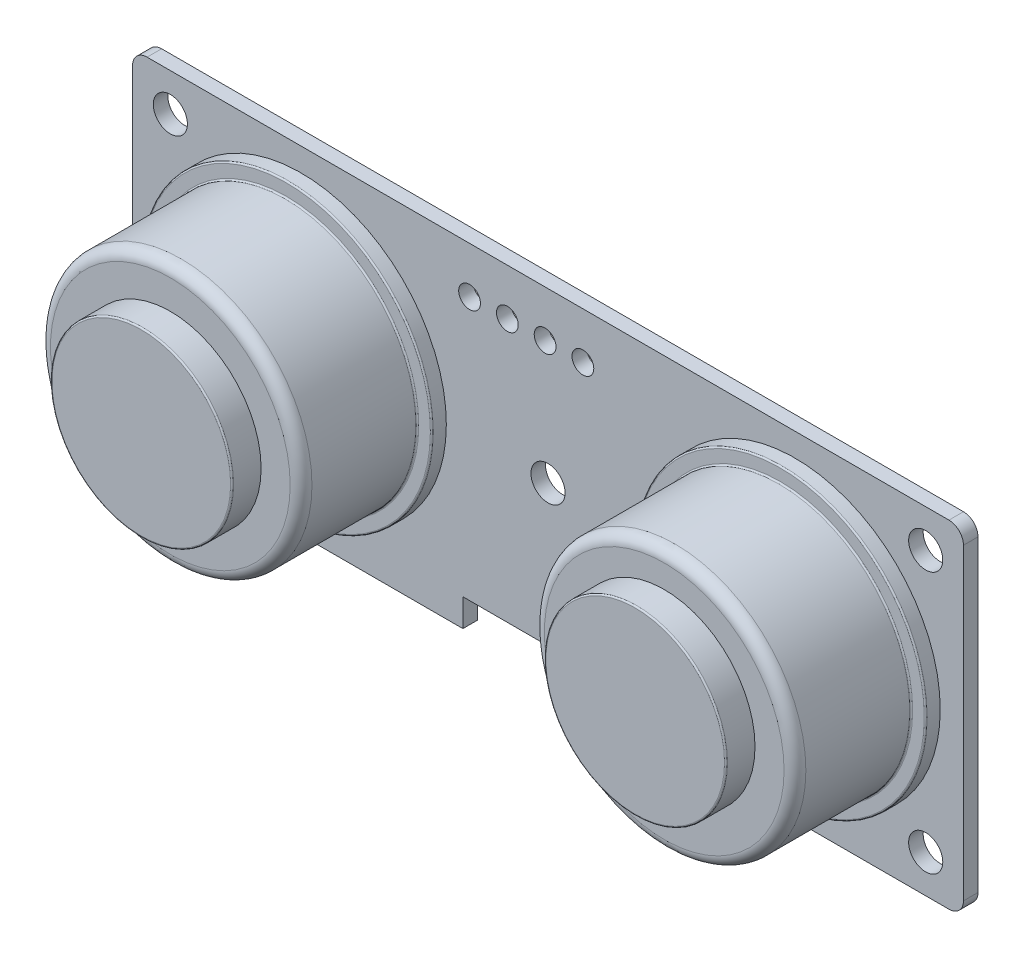
SolidWorks part; units mm, degrees
ref_plane "Ön Düzlem" through (0, 0, 0) normal (0, 0, 1) x (1, 0, 0)
ref_plane "Üst Düzlem" through (0, 0, 0) normal (0, 1, 0) x (1, 0, 0)
ref_plane "Sağ Düzlem" through (0, 0, 0) normal (1, 0, 0) x (0, 0, -1)
sketch "Çizim1" plane through (0, 0, 0) normal (0, 0, 1) x (1, 0, 0)
  line L0 (-5.8595, -11.6) -> (-27.6, -11.6)
  line L1 (27.6, 11.6) -> (-27.6, 11.6)
  line L2 (28.6, 10.6) -> (28.6, -10.6)
  line L3 (27.6, -11.6) -> (5.8595, -11.6)
  line L4 (-28.6, 10.6) -> (-28.6, -10.6)
  line L5 (0, 0) -> (0, -9.6979) construction
  line L6 (0, 0) -> (-28.6, 0) construction
  line L7 (-5.8595, -9.6979) -> (5.8595, -9.6979)
  line L8 (-5.8595, -9.6979) -> (-5.8595, -11.6)
  line L10 (5.8595, -9.6979) -> (5.8595, -11.6)
  line L11 (0, 0) -> (0, 11.6) construction
  line L12 (-26, 9) -> (26, 9) construction
  line L13 (-17.1, 5.1) -> (-17.1, -5.1) construction
  line L14 (-5.4, 8.4) -> (2.6, 8.4) construction
  arc A0 (28.6, -10.6) -> (27.6, -11.6) centre (27.6, -10.6) cw
  arc A1 (27.6, 11.6) -> (28.6, 10.6) centre (27.6, 10.6) cw
  arc A2 (-27.6, -11.6) -> (-28.6, -10.6) centre (-27.6, -10.6) cw
  arc A3 (-27.6, 11.6) -> (-28.6, 10.6) centre (-27.6, 10.6) ccw
  circle A4 centre (-26, 9) radius 1.175
  circle A5 centre (26, 9) radius 1.175
  circle A6 centre (26, -9) radius 1.175
  circle A7 centre (-26, -9) radius 1.175
  circle A8 centre (0, 0) radius 1.175
  circle A9 centre (-17.1, 5.1) radius 0.9
  circle A10 centre (-17.1, -5.1) radius 0.9
  circle A11 centre (17.1, -5.1) radius 0.9
  circle A12 centre (17.1, 5.1) radius 0.9
  circle A13 centre (-5.4, 8.4) radius 0.75
  circle A14 centre (-2.8, 8.4) radius 0.75
  circle A15 centre (-0.2, 8.4) radius 0.75
  circle A16 centre (2.4, 8.4) radius 0.75
  point P1 (0, 5.8)
  point P29 (0, 9)
  dimension "D3" = 1
  dimension "D4" = 2.35
  dimension "D5" = 52
  dimension "D6" = 2.35
  dimension "D7" = 6.5
  dimension "D8" = 6.5
  dimension "D9" = 2.6
  dimension "D10" = 2.6
  dimension "D11" = 2.6
  dimension "D12" = 2.6
  dimension "D13" = 18
  dimension "D15" = 1.8
  dimension "D16" = 1.8
  dimension "D20" = 1.5
  dimension "D1" = 57.2
  dimension "D2" = 23.2
  dimension "D14" = 11.5
  dimension "D17" = 8
  dimension "D18" = 3.2
  dimension "D19" = 23.2
  dimension "D21" = 4
extrude "Yükseklik-Ekstrüzyon1" add sketch "Çizim1" along normal blind 1
sketch "Çizim2" plane through (0, 0, 1) normal (0, 0, 1) x (1, 0, 0)
  line L3 (-17, 0) -> (17, 0) construction
  line L4 (0, 1.175) -> (0, -1.175) construction
  circle A0 centre (-17, 0) radius 10
  circle A1 centre (17, 0) radius 10
  circle A2 centre (0, 0) radius 1.175 construction
  point P8 (0, 0)
  dimension "D1" = 20
  dimension "D2" = 34
  dimension "D6" = 20
extrude "Yükseklik-Ekstrüzyon2" add sketch "Çizim2" along normal blind 1 separate body
sketch "Çizim3" plane through (0, 0, 2) normal (0, 0, 1) x (1, 0, 0)
  circle A0 centre (-17, 0) radius 9
  circle A1 centre (17, 0) radius 9
  dimension "D1" = 18
extrude "Yükseklik-Ekstrüzyon3" add sketch "Çizim3" along normal blind 8
sketch "Çizim4" plane through (0, 0, 10) normal (0, 0, 1) x (1, 0, 0)
  circle A0 centre (-17, 0) radius 6.25
  circle A1 centre (17, 0.4139) radius 6.25
  dimension "D1" = 12.5
extrude "Yükseklik-Ekstrüzyon4" add sketch "Çizim4" along normal blind 2 separate body
fillet "Radyus1" radius 0.75 1 edges at (-8, 0, 10)
fillet "Radyus2" radius 0.75 1 edges at (26, 0, 10)
fillet "Radyus3" radius 0.1 1 edges at (-10.75, 0, 12)
fillet "Radyus4" radius 0.1 1 edges at (23.25, 0.4139, 12)
fillet "Radyus5" radius 0.1 2 edges at (-7, 0, 2) (-8, 0, 2)
fillet "Radyus6" radius 0.1 2 edges at (27, 0, 2) (26, 0, 2)
sketch "Çizim10" plane through (0, 0, 0) normal (0, 0, -1) x (-1, 0, 0)
  line L0 (-13.9117, 4.4086) -> (-5.092, 4.4086)
  line L2 (-13.9117, 4.4086) -> (-13.9117, 1.1362)
  line L3 (-13.9117, 1.1362) -> (-5.092, 1.1362)
  line L4 (-5.092, 4.4086) -> (-5.092, 1.1362)
  line L5 (4.9259, -2.3247) -> (9.1781, -2.3247)
  line L6 (4.9259, -2.3247) -> (4.9259, -8.8397)
  line L7 (4.9259, -8.8397) -> (9.1781, -8.8397)
  line L8 (9.1781, -2.3247) -> (9.1781, -8.8397)
  line L21 (-22.8585, 6.7991) -> (-19.9987, 6.7991)
  line L22 (-22.8585, 6.7991) -> (-22.8585, 5.55)
  line L23 (-22.8585, 5.55) -> (-19.9987, 5.55)
  line L24 (-19.9987, 6.7991) -> (-19.9987, 5.55)
  line L54 (-13.9117, 2.7724) -> (-5.092, 2.7724) construction
  line L83 (-21.4286, 5.55) -> (-21.4286, 6.7991) construction
  line L137 (7.052, -2.3247) -> (7.052, -8.8397) construction
  line L180 (11.2809, 9.5742) -> (12.8042, 9.5742)
  line L181 (11.2809, 7.4761) -> (12.8042, 7.4761)
  line L184 (11.2809, 9.5742) -> (11.2809, 7.4761)
  line L185 (12.8042, 9.5742) -> (12.8042, 7.4761)
  line L187 (21.6705, 8.5491) -> (21.6705, 6.4509)
  line L189 (23.1938, 8.5491) -> (23.1938, 6.4509)
  line L192 (21.6705, 8.5491) -> (23.1938, 8.5491)
  line L196 (21.6705, 6.4509) -> (23.1938, 6.4509)
  line L210 (15.5044, 1.6587) -> (15.5044, 2.9078)
  line L212 (12.6446, 1.6587) -> (12.6446, 2.9078)
  line L214 (15.5044, 1.6587) -> (12.6446, 1.6587)
  line L220 (15.5044, 2.9078) -> (12.6446, 2.9078)
  line L222 (14.0745, 2.9078) -> (14.0745, 1.6587) construction
  line L227 (-3.9914, -8.0653) -> (-1.1316, -8.0653)
  line L229 (-3.9914, -6.8162) -> (-1.1316, -6.8162)
  line L236 (-1.1316, -6.8162) -> (-1.1316, -8.0653)
  line L237 (-3.9914, -6.8162) -> (-3.9914, -8.0653)
  line L243 (-2.5615, -8.0653) -> (-2.5615, -6.8162) construction
  line L244 (8.651, 5.9274) -> (8.651, 3.8292)
  line L245 (10.1743, 5.9274) -> (10.1743, 3.8292)
  line L246 (8.651, 3.8292) -> (10.1743, 3.8292)
  line L247 (8.651, 5.9274) -> (10.1743, 5.9274)
  point P92 (-21.4286, 6.8907)
  point P209 (14.0745, 1.5672)
  point P224 (-2.5615, -6.7247)
extrude "Yükseklik-Ekstrüzyon7" add sketch "Çizim10" along normal blind 1
sketch "Çizim11" plane through (0, 0, 0) normal (0, 0, -1) x (-1, 0, 0)
  line L0 (11.2809, 10.1474) -> (12.8042, 10.1474)
  line L1 (11.2809, 10.1474) -> (11.2809, 9.6474)
  line L2 (11.2809, 6.8956) -> (12.8042, 6.8956)
  line L3 (12.8042, 10.1474) -> (12.8042, 9.6474)
  line L4 (-13.7663, 4.4644) -> (-13.7663, 5.8674)
  line L5 (-13.7663, 5.8674) -> (-13.2262, 5.8674)
  line L6 (-13.2262, 4.4644) -> (-13.2262, 5.8674)
  line L7 (-13.7663, 4.4644) -> (-13.2262, 4.4644)
  line L8 (-11.8762, 4.4644) -> (-11.8762, 5.8674)
  line L9 (-12.4163, 5.8674) -> (-11.8762, 5.8674)
  line L10 (-12.4163, 4.4644) -> (-12.4163, 5.8674)
  line L11 (-12.4163, 4.4644) -> (-11.8762, 4.4644)
  line L12 (-10.5262, 4.4644) -> (-10.5262, 5.8674)
  line L13 (-11.0663, 5.8674) -> (-10.5262, 5.8674)
  line L14 (-11.0663, 4.4644) -> (-11.0663, 5.8674)
  line L15 (-11.0663, 4.4644) -> (-10.5262, 4.4644)
  line L16 (-9.1762, 4.4644) -> (-9.1762, 5.8674)
  line L17 (-9.7163, 5.8674) -> (-9.1762, 5.8674)
  line L18 (-9.7163, 4.4644) -> (-9.7163, 5.8674)
  line L19 (-9.7163, 4.4644) -> (-9.1762, 4.4644)
  line L20 (-7.8262, 4.4644) -> (-7.8262, 5.8674)
  line L21 (-8.3663, 5.8674) -> (-7.8262, 5.8674)
  line L22 (-8.3663, 4.4644) -> (-8.3663, 5.8674)
  line L23 (-8.3663, 4.4644) -> (-7.8262, 4.4644)
  line L24 (-6.4762, 4.4644) -> (-6.4762, 5.8674)
  line L25 (-7.0163, 5.8674) -> (-6.4762, 5.8674)
  line L26 (-7.0163, 4.4644) -> (-7.0163, 5.8674)
  line L27 (-7.0163, 4.4644) -> (-6.4762, 4.4644)
  line L28 (-5.1262, 4.4644) -> (-5.1262, 5.8674)
  line L29 (-5.6663, 5.8674) -> (-5.1262, 5.8674)
  line L30 (-5.6663, 4.4644) -> (-5.6663, 5.8674)
  line L31 (-5.6663, 4.4644) -> (-5.1262, 4.4644)
  line L32 (-5.6663, 1.0904) -> (-5.1262, 1.0904)
  line L33 (-5.6663, 1.0904) -> (-5.6663, -0.3126)
  line L34 (-5.6663, -0.3126) -> (-5.1262, -0.3126)
  line L35 (-5.1262, 1.0904) -> (-5.1262, -0.3126)
  line L36 (-7.0163, 1.0904) -> (-6.4762, 1.0904)
  line L37 (-7.0163, 1.0904) -> (-7.0163, -0.3126)
  line L38 (-7.0163, -0.3126) -> (-6.4762, -0.3126)
  line L39 (-6.4762, 1.0904) -> (-6.4762, -0.3126)
  line L40 (-8.3663, 1.0904) -> (-7.8262, 1.0904)
  line L41 (-8.3663, 1.0904) -> (-8.3663, -0.3126)
  line L42 (-8.3663, -0.3126) -> (-7.8262, -0.3126)
  line L43 (-7.8262, 1.0904) -> (-7.8262, -0.3126)
  line L44 (-9.7163, 1.0904) -> (-9.1762, 1.0904)
  line L45 (-9.7163, 1.0904) -> (-9.7163, -0.3126)
  line L46 (-9.7163, -0.3126) -> (-9.1762, -0.3126)
  line L47 (-9.1762, 1.0904) -> (-9.1762, -0.3126)
  line L48 (-11.0663, 1.0904) -> (-10.5262, 1.0904)
  line L49 (-11.0663, 1.0904) -> (-11.0663, -0.3126)
  line L50 (-11.0663, -0.3126) -> (-10.5262, -0.3126)
  line L51 (-10.5262, 1.0904) -> (-10.5262, -0.3126)
  line L52 (-12.4163, 1.0904) -> (-11.8762, 1.0904)
  line L53 (-12.4163, 1.0904) -> (-12.4163, -0.3126)
  line L54 (-12.4163, -0.3126) -> (-11.8762, -0.3126)
  line L55 (-11.8762, 1.0904) -> (-11.8762, -0.3126)
  line L56 (-13.7663, 1.0904) -> (-13.2262, 1.0904)
  line L57 (-13.2262, 1.0904) -> (-13.2262, -0.3126)
  line L58 (-13.7663, -0.3126) -> (-13.2262, -0.3126)
  line L59 (-13.7663, 1.0904) -> (-13.7663, -0.3126)
  line L60 (-22.8585, 5.505) -> (-22.0979, 5.505)
  line L61 (-22.8585, 5.505) -> (-22.8585, 4.6135)
  line L62 (-22.8585, 4.6135) -> (-22.0979, 4.6135)
  line L63 (-22.0979, 5.505) -> (-22.0979, 4.6135)
  line L64 (-19.9987, 4.6135) -> (-20.7593, 4.6135)
  line L65 (-20.7593, 5.505) -> (-20.7593, 4.6135)
  line L66 (-19.9987, 5.505) -> (-20.7593, 5.505)
  line L67 (-19.9987, 5.505) -> (-19.9987, 4.6135)
  line L68 (-21.9148, 6.8541) -> (-20.9424, 6.8541)
  line L69 (-20.9424, 6.8541) -> (-20.9424, 7.6725)
  line L70 (-20.9424, 7.6725) -> (-21.9148, 7.6725)
  line L71 (-21.9148, 6.8541) -> (-21.9148, 7.6725)
  line L72 (3.2713, -2.9897) -> (3.2713, -3.4612)
  line L73 (3.2713, -2.3197) -> (4.8588, -2.3197)
  line L74 (3.2713, -2.3197) -> (3.2713, -2.7912)
  line L75 (3.2713, -2.7912) -> (4.8588, -2.7912)
  line L76 (4.8588, -2.3197) -> (4.8588, -2.7912)
  line L77 (3.2713, -2.9897) -> (4.8588, -2.9897)
  line L78 (4.8588, -2.9897) -> (4.8588, -3.4612)
  line L79 (3.2713, -3.4612) -> (4.8588, -3.4612)
  line L80 (3.2713, -3.6597) -> (3.2713, -4.1312)
  line L81 (3.2713, -3.6597) -> (4.8588, -3.6597)
  line L82 (4.8588, -3.6597) -> (4.8588, -4.1312)
  line L83 (3.2713, -4.1312) -> (4.8588, -4.1312)
  line L84 (3.2713, -4.3297) -> (3.2713, -4.8012)
  line L85 (3.2713, -4.3297) -> (4.8588, -4.3297)
  line L86 (4.8588, -4.3297) -> (4.8588, -4.8012)
  line L87 (3.2713, -4.8012) -> (4.8588, -4.8012)
  line L88 (3.2713, -4.9997) -> (3.2713, -5.4712)
  line L89 (3.2713, -4.9997) -> (4.8588, -4.9997)
  line L90 (4.8588, -4.9997) -> (4.8588, -5.4712)
  line L91 (3.2713, -5.4712) -> (4.8588, -5.4712)
  line L92 (3.2713, -5.6697) -> (3.2713, -6.1412)
  line L93 (3.2713, -5.6697) -> (4.8588, -5.6697)
  line L94 (4.8588, -5.6697) -> (4.8588, -6.1412)
  line L95 (3.2713, -6.1412) -> (4.8588, -6.1412)
  line L96 (3.2713, -6.3397) -> (3.2713, -6.8112)
  line L97 (3.2713, -6.3397) -> (4.8588, -6.3397)
  line L98 (4.8588, -6.3397) -> (4.8588, -6.8112)
  line L99 (3.2713, -6.8112) -> (4.8588, -6.8112)
  line L100 (3.2713, -7.0097) -> (3.2713, -7.4812)
  line L101 (3.2713, -7.0097) -> (4.8588, -7.0097)
  line L102 (4.8588, -7.0097) -> (4.8588, -7.4812)
  line L103 (3.2713, -7.4812) -> (4.8588, -7.4812)
  line L104 (3.2713, -7.6797) -> (3.2713, -8.1512)
  line L105 (3.2713, -7.6797) -> (4.8588, -7.6797)
  line L106 (4.8588, -7.6797) -> (4.8588, -8.1512)
  line L107 (3.2713, -8.1512) -> (4.8588, -8.1512)
  line L108 (3.2713, -8.3497) -> (3.2713, -8.8212)
  line L109 (3.2713, -8.3497) -> (4.8588, -8.3497)
  line L110 (4.8588, -8.3497) -> (4.8588, -8.8212)
  line L111 (3.2713, -8.8212) -> (4.8588, -8.8212)
  line L112 (10.8327, -8.8212) -> (9.2452, -8.8212)
  line L113 (9.2452, -8.3497) -> (9.2452, -8.8212)
  line L114 (10.8327, -8.3497) -> (9.2452, -8.3497)
  line L115 (10.8327, -8.3497) -> (10.8327, -8.8212)
  line L116 (10.8327, -8.1512) -> (9.2452, -8.1512)
  line L117 (9.2452, -7.6797) -> (9.2452, -8.1512)
  line L118 (10.8327, -7.6797) -> (9.2452, -7.6797)
  line L119 (10.8327, -7.6797) -> (10.8327, -8.1512)
  line L120 (10.8327, -7.4812) -> (9.2452, -7.4812)
  line L121 (9.2452, -7.0097) -> (9.2452, -7.4812)
  line L122 (10.8327, -7.0097) -> (9.2452, -7.0097)
  line L123 (10.8327, -7.0097) -> (10.8327, -7.4812)
  line L124 (10.8327, -6.8112) -> (9.2452, -6.8112)
  line L125 (9.2452, -6.3397) -> (9.2452, -6.8112)
  line L126 (10.8327, -6.3397) -> (9.2452, -6.3397)
  line L127 (10.8327, -6.3397) -> (10.8327, -6.8112)
  line L128 (10.8327, -6.1412) -> (9.2452, -6.1412)
  line L129 (9.2452, -5.6697) -> (9.2452, -6.1412)
  line L130 (10.8327, -5.6697) -> (9.2452, -5.6697)
  line L131 (10.8327, -5.6697) -> (10.8327, -6.1412)
  line L132 (10.8327, -5.4712) -> (9.2452, -5.4712)
  line L133 (9.2452, -4.9997) -> (9.2452, -5.4712)
  line L134 (10.8327, -4.9997) -> (9.2452, -4.9997)
  line L135 (10.8327, -4.9997) -> (10.8327, -5.4712)
  line L136 (10.8327, -4.8012) -> (9.2452, -4.8012)
  line L137 (9.2452, -4.3297) -> (9.2452, -4.8012)
  line L138 (10.8327, -4.3297) -> (9.2452, -4.3297)
  line L139 (10.8327, -4.3297) -> (10.8327, -4.8012)
  line L140 (10.8327, -4.1312) -> (9.2452, -4.1312)
  line L141 (9.2452, -3.6597) -> (9.2452, -4.1312)
  line L142 (10.8327, -3.6597) -> (9.2452, -3.6597)
  line L143 (10.8327, -3.6597) -> (10.8327, -4.1312)
  line L144 (10.8327, -3.4612) -> (9.2452, -3.4612)
  line L145 (9.2452, -2.9897) -> (9.2452, -3.4612)
  line L146 (10.8327, -2.9897) -> (9.2452, -2.9897)
  line L147 (9.2452, -2.3197) -> (9.2452, -2.7912)
  line L148 (10.8327, -2.7912) -> (9.2452, -2.7912)
  line L149 (10.8327, -2.3197) -> (10.8327, -2.7912)
  line L150 (10.8327, -2.3197) -> (9.2452, -2.3197)
  line L151 (10.8327, -2.9897) -> (10.8327, -3.4612)
  line L152 (11.2809, 9.6474) -> (12.8042, 9.6474)
  line L153 (11.2809, 7.3956) -> (12.8042, 7.3956)
  line L154 (11.2809, 7.3956) -> (11.2809, 6.8956)
  line L155 (12.8042, 7.3956) -> (12.8042, 6.8956)
  line L156 (23.1938, 9.1223) -> (23.1938, 8.6223)
  line L157 (23.1938, 6.3705) -> (23.1938, 5.8705)
  line L158 (21.6705, 9.1223) -> (21.6705, 8.6223)
  line L159 (21.6705, 8.6223) -> (23.1938, 8.6223)
  line L160 (21.6705, 5.8705) -> (23.1938, 5.8705)
  line L161 (21.6705, 6.3705) -> (21.6705, 5.8705)
  line L162 (21.6705, 6.3705) -> (23.1938, 6.3705)
  line L163 (21.6705, 9.1223) -> (23.1938, 9.1223)
  line L164 (14.7438, 2.9628) -> (14.7438, 3.8543)
  line L165 (12.6446, 2.9628) -> (13.4052, 2.9628)
  line L166 (13.5883, 1.6137) -> (13.5883, 0.7953)
  line L167 (15.5044, 2.9628) -> (15.5044, 3.8543)
  line L168 (15.5044, 2.9628) -> (14.7438, 2.9628)
  line L169 (12.6446, 3.8543) -> (13.4052, 3.8543)
  line L170 (14.5607, 1.6137) -> (14.5607, 0.7953)
  line L171 (13.4052, 2.9628) -> (13.4052, 3.8543)
  line L172 (14.5607, 1.6137) -> (13.5883, 1.6137)
  line L173 (15.5044, 3.8543) -> (14.7438, 3.8543)
  line L174 (12.6446, 2.9628) -> (12.6446, 3.8543)
  line L175 (13.5883, 0.7953) -> (14.5607, 0.7953)
  line L176 (-2.0753, -6.7612) -> (-2.0753, -5.9428)
  line L177 (-1.8922, -8.1103) -> (-1.8922, -9.0018)
  line L178 (-3.2308, -8.1103) -> (-3.2308, -9.0018)
  line L179 (-1.1316, -9.0018) -> (-1.8922, -9.0018)
  line L180 (-3.0477, -6.7612) -> (-2.0753, -6.7612)
  line L181 (-3.9914, -8.1103) -> (-3.9914, -9.0018)
  line L182 (-3.9914, -8.1103) -> (-3.2308, -8.1103)
  line L183 (-3.9914, -9.0018) -> (-3.2308, -9.0018)
  line L184 (-3.0477, -6.7612) -> (-3.0477, -5.9428)
  line L185 (-1.1316, -8.1103) -> (-1.8922, -8.1103)
  line L186 (-1.1316, -8.1103) -> (-1.1316, -9.0018)
  line L187 (-2.0753, -5.9428) -> (-3.0477, -5.9428)
  line L188 (10.1743, 6.5142) -> (10.1743, 6.0142)
  line L189 (8.651, 6.5142) -> (8.651, 6.0142)
  line L190 (8.651, 3.7624) -> (8.651, 3.2624)
  line L191 (10.1743, 3.7624) -> (10.1743, 3.2624)
  line L192 (8.651, 6.0142) -> (10.1743, 6.0142)
  line L193 (8.651, 6.5142) -> (10.1743, 6.5142)
  line L194 (8.651, 3.7624) -> (10.1743, 3.7624)
  line L195 (8.651, 3.2624) -> (10.1743, 3.2624)
extrude "Yükseklik-Ekstrüzyon8" add sketch "Çizim11" along normal blind 1
fillet "Radyus8" radius 0.5 49 edges at (3.6111, -9.0018, -1) (1.5119, -9.0018, -1) (2.5615, -5.9428, -1) (-3.2713, -2.5555, -1) (-3.2713, -3.2255, -1) (-3.2713, -3.8955, -1) (-3.2713, -4.5655, -1) (-3.2713, -5.2355, -1) (-3.2713, -5.9055, -1) (-3.2713, -6.5755, -1) (-3.2713, -7.2455, -1) (-3.2713, -7.9155, -1) (-3.2713, -8.5855, -1) (-10.8327, -8.5855, -1) (-10.8327, -7.9155, -1) (-10.8327, -7.2455, -1) (-10.8327, -6.5755, -1) (-10.8327, -5.9055, -1) (-10.8327, -5.2355, -1) (-10.8327, -4.5655, -1) (-10.8327, -3.8955, -1) (-10.8327, -3.2255, -1) (-10.8327, -2.5555, -1) (-14.0745, 0.7953, -1) (-15.1241, 3.8543, -1) (-13.0249, 3.8543, -1) (-22.4322, 5.8705, -1) (-22.4322, 9.1223, -1) (-12.0425, 6.8956, -1) (-12.0425, 10.1474, -1) (5.3962, -0.3126, -1) (6.7462, -0.3126, -1) (8.0962, -0.3126, -1) (9.4462, -0.3126, -1) (10.7962, -0.3126, -1) (12.1462, -0.3126, -1) (13.4962, -0.3126, -1) (5.3962, 5.8674, -1) (6.7462, 5.8674, -1) (8.0962, 5.8674, -1) (9.4462, 5.8674, -1) (10.7962, 5.8674, -1) (12.1462, 5.8674, -1) (13.4962, 5.8674, -1) (20.379, 4.6135, -1) (22.4782, 4.6135, -1) (21.4286, 7.6725, -1) (-9.4126, 3.2624, -1) (-9.4126, 6.5142, -1)
ref_axis "Axis1" through (2.4, 8.4, 1) along (0, 0, -1)
ref_axis "Axis2" through (-5.4, 8.4, 1) along (0, 0, -1)
ref_point "Point1"
ref_point "Point2"
ref_axis "Axis3" through (-5.4, 8.4, 0.5) along (1, 0, 0)
ref_plane "Plane3" through (0, 8.4, 0) normal (0, -1, 0) x (-1, 0, 0)
ref_plane "Plane5" through (2.4, 0, 0) normal (-1, 0, 0) x (0, 0, -1)
ref_plane "Plane6" through (-5.4, 0, 0) normal (-1, 0, 0) x (0, 0, -1)
ref_plane "Plane7" through (-1.5, 0, 0) normal (-1, 0, 0) x (0, 0, 1)
